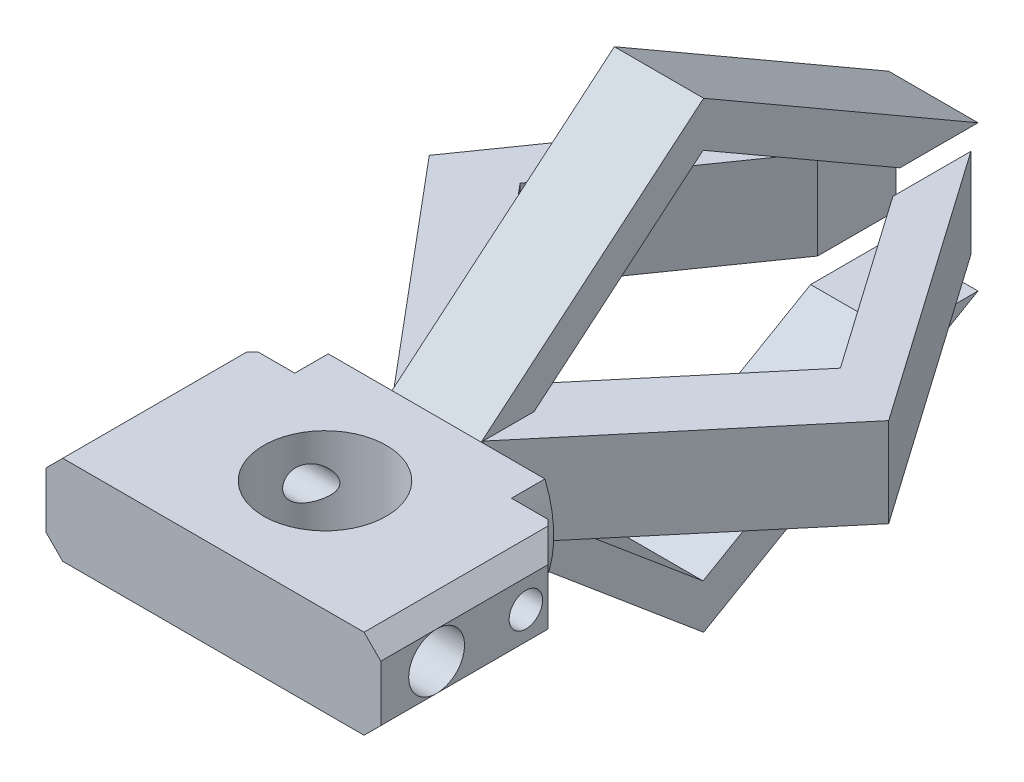
SolidWorks part; units mm, degrees
ref_plane "Ön Düzlem" through (0, 0, 0) normal (0, 0, 1) x (1, 0, 0)
ref_plane "Üst Düzlem" through (0, 0, 0) normal (0, 1, 0) x (1, 0, 0)
ref_plane "Sağ Düzlem" through (0, 0, 0) normal (1, 0, 0) x (0, 0, -1)
sketch "Çizim2" plane through (0, 0, 0) normal (0, 0, 1) x (1, 0, 0)
  circle A0 centre (0, 0) radius 10.5
  dimension "D1" = 21
extrude "Yükseklik-Ekstrüzyon1" add sketch "Çizim2" along normal blind 3
sketch "Çizim3" plane through (0, 0, 0) normal (0, 1, 0) x (1, 0, 0)
  line L0 (-14.3497, 21.8326) -> (0, 4.7312)
  line L1 (-3.8625, 0) -> (3.8625, 0)
  line L2 (10.5, 0) -> (-10.5, 0) construction
  line L3 (3.8625, 0) -> (20.5845, 19.9285)
  line L4 (20.5845, 19.9285) -> (3.3695, 44.5141)
  line L5 (-3.8625, 0) -> (-20.5845, 19.9285)
  line L6 (3.3695, 44.5141) -> (3.3695, 37.5141)
  line L7 (3.3695, 37.5141) -> (14.3497, 21.8326)
  line L8 (-20.5845, 19.9285) -> (-3.3695, 44.5141)
  line L9 (14.3497, 21.8326) -> (0, 4.7312)
  line L16 (-3.3695, 44.5141) -> (-3.3695, 37.5141)
  line L17 (-3.3695, 37.5141) -> (-14.3497, 21.8326)
  dimension "D1" = 7
  dimension "D2" = 50
  dimension "D3" = 105
  dimension "D4" = 6
extrude "Yükseklik-Ekstrüzyon3" add sketch "Çizim3" along normal blind 4 and the other way blind 4
sketch "Çizim4" plane through (0, 0, 0) normal (1, 0, 0) x (0, 0, -1)
  line L0 (44.5141, 6.5275) -> (37.5141, 6.5275)
  line L3 (4.7312, 4) -> (4.7312, -4)
  line L4 (19.9285, 20.722) -> (0, 4)
  line L5 (0, -4) -> (0, 4)
  line L6 (44.5141, 6.5275) -> (19.9285, 20.722)
  line L7 (37.5141, 6.5275) -> (19.8781, 16.7097)
  line L8 (19.8781, 16.7097) -> (4.7312, 4)
  line L11 (44.5141, -6.5275) -> (37.5141, -6.5275)
  line L12 (44.5141, -6.5275) -> (19.9285, -20.722)
  line L13 (37.5141, -6.5275) -> (19.8781, -16.7097)
  line L14 (19.8781, -16.7097) -> (4.7312, -4)
  line L15 (19.9285, -20.722) -> (0, -4)
  dimension "D1" = 7
extrude "Yükseklik-Ekstrüzyon6" add sketch "Çizim4" against normal blind 4 and the other way blind 4
sketch "Çizim5" plane through (0, 0, 3) normal (0, 0, 1) x (1, 0, 0)
  line L0 (-20.5845, 4) -> (-4, 4) construction
  line L1 (-11.1715, 4) -> (12.2473, 4)
  line L2 (-11.1715, 4) -> (-11.1715, 11.3784)
  line L3 (-11.1715, 11.3784) -> (12.2473, 11.3784)
  line L4 (12.2473, 4) -> (12.2473, 11.3784)
  line L5 (-20.5845, -4) -> (-4, -4) construction
  line L6 (-11.1715, -4) -> (12.2473, -4)
  line L7 (-11.1715, -4) -> (-11.1715, -12.7024)
  line L8 (-11.1715, -12.7024) -> (12.2473, -12.7024)
  line L9 (12.2473, -4) -> (12.2473, -12.7024)
extrude "Kes-Ekstrüzyon1" cut sketch "Çizim5" against normal up to surface (3 mm away) up to face at (10.5, 0, 0)
sketch "Çizim6" plane through (0, 0, 3) normal (0, 0, 1) x (1, 0, 0)
  line L0 (-20.5845, 4) -> (-4, 4) construction
  line L1 (-15, 4) -> (15, 4)
  line L2 (-15, 4) -> (-15, -4)
  line L3 (-15, -4) -> (15, -4)
  line L4 (15, 4) -> (15, -4)
  line L5 (4, -4) -> (20.5845, -4) construction
  dimension "D1" = 30
  dimension "D2" = 15
extrude "Yükseklik-Ekstrüzyon7" add sketch "Çizim6" along normal blind 17
sketch "Çizim7" plane through (15, 0, 0) normal (1, 0, 0) x (0, 0, -1)
  line L0 (-20, -4) -> (-20, 4) construction
  circle A0 centre (-15, 0) radius 2.5
  dimension "D1" = 5
  dimension "D2" = 5
extrude "Kes-Ekstrüzyon2" cut sketch "Çizim7" against normal up to surface (30 mm away) up to face at (-15, 0, 11.5)
sketch "Çizim8" plane through (-15, 0, 0) normal (-1, 0, 0) x (0, 0, 1)
  circle A1 centre (7, 0) radius 1.5
  dimension "D2" = 3
extrude "Kes-Ekstrüzyon3" cut sketch "Çizim8" against normal up to surface (30 mm away) up to face at (15, 2.5, 15)
chamfer "Pah1" distance 1.5 angle 45 4 edges at (15, -4, 11.5) (15, 4, 11.5) (-15, -4, 11.5) (-15, 4, 11.5)
chamfer "Pah2" distance 2 angle 45 2 edges at (15, 0, 3) (-15, 0, 3)
sketch "Çizim9" plane through (0, 4, 0) normal (0, 1, 0) x (1, 0, 0)
  line L0 (9.7082, 0) -> (4, 0) construction
  circle A0 centre (0, -10) radius 5.5
  dimension "D1" = 10
  dimension "D2" = 11
extrude "Kes-Ekstrüzyon4" cut sketch "Çizim9" against normal blind 17
